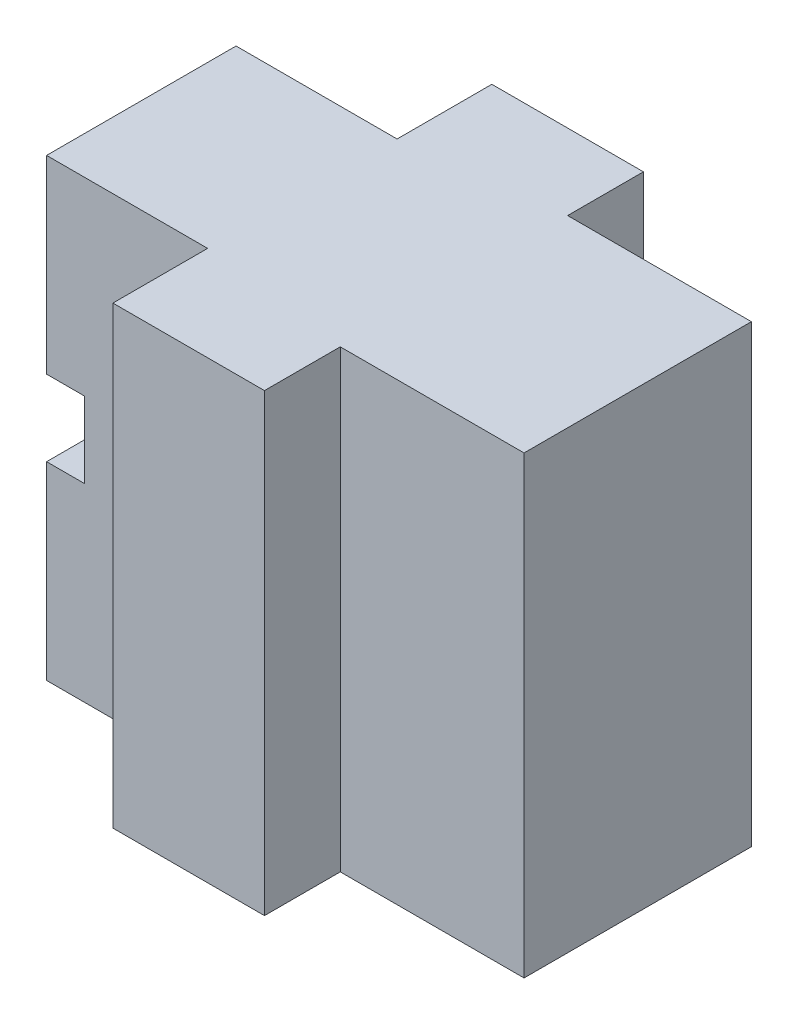
SolidWorks part; units mm, degrees
ref_plane "Front" through (0, 0, 0) normal (0, 0, 1) x (1, 0, 0)
ref_plane "Top" through (0, 0, 0) normal (0, 1, 0) x (1, 0, 0)
ref_plane "Right" through (0, 0, 0) normal (1, 0, 0) x (0, 0, -1)
sketch "Body1_Sketch" plane through (0, 0, 0) normal (0, 0, 1) x (1, 0, 0)
  line L0 (-16.5, -12) -> (-16.5, -2)
  line L1 (-16.5, -2) -> (-14.5, -2)
  line L2 (-14.5, -2) -> (-14.5, 2)
  line L3 (-14.5, 2) -> (-16.5, 2)
  line L4 (-16.5, 2) -> (-16.5, 12)
  line L5 (-16.5, 12) -> (0, 12)
  line L6 (0, 12) -> (0, -12)
  line L7 (0, -12) -> (-16.5, -12)
  point P7 (0, 0)
  dimension "J" = 24
  dimension "L" = 4
  dimension "M" = 2
  dimension "K" = 10
  dimension "AA-G-H+I" = 16.5
extrude "Body1" add sketch "Body1_Sketch" along normal mid plane 10
sketch "Body2_Sketch" plane through (0, 0, 0) normal (0, 0, 1) x (1, 0, 0)
  line L0 (0, 12) -> (-8, 12)
  line L1 (0, -12) -> (0, 12)
  line L2 (-8, -12) -> (0, -12)
  line L3 (0, 12) -> (-16.5, 12) construction
  line L4 (-16.5, -12) -> (0, -12) construction
  line L5 (0, -12) -> (0, 12) construction
  line L6 (-8, 12) -> (-8, -12)
  dimension "I" = 8
extrude "Body2" add sketch "Body2_Sketch" along normal mid plane 20
sketch "Cut_Sketch" plane through (-16.5, 0, 0) normal (-1, 0, 0) x (0, 0, 1)
  line L1 (0, -50) -> (0, 50) construction
  line L2 (5, -12) -> (-5, -12) construction
  circle A0 centre (0, 7) radius 2.5
  circle A1 centre (0, -7) radius 2.5
  dimension "D1" = 5
  dimension "O" = 5
  dimension "Q" = 14
extrude "Cut" cut sketch "Cut_Sketch" against normal blind 10
sketch "Sketch2" plane through (0, 12, 0) normal (0, 1, 0) x (-1, 0, 0)
  line L0 (0, 10) -> (0, -10) construction
  line L1 (0, 6) -> (-9.7, 6)
  line L2 (0, 6) -> (0, -6)
  line L3 (0, -6) -> (-9.7, -6)
  line L4 (-9.7, 6) -> (-9.7, -6)
  line L5 (8, 10) -> (8, 5) construction
  point P6 (-9.7, 0)
  dimension "NC" = 12
  dimension "H" = 17.7
extrude "L-Detail" add sketch "Sketch2" against normal up to surface (24 mm away) up to face at (-8.125, -12, 0)
